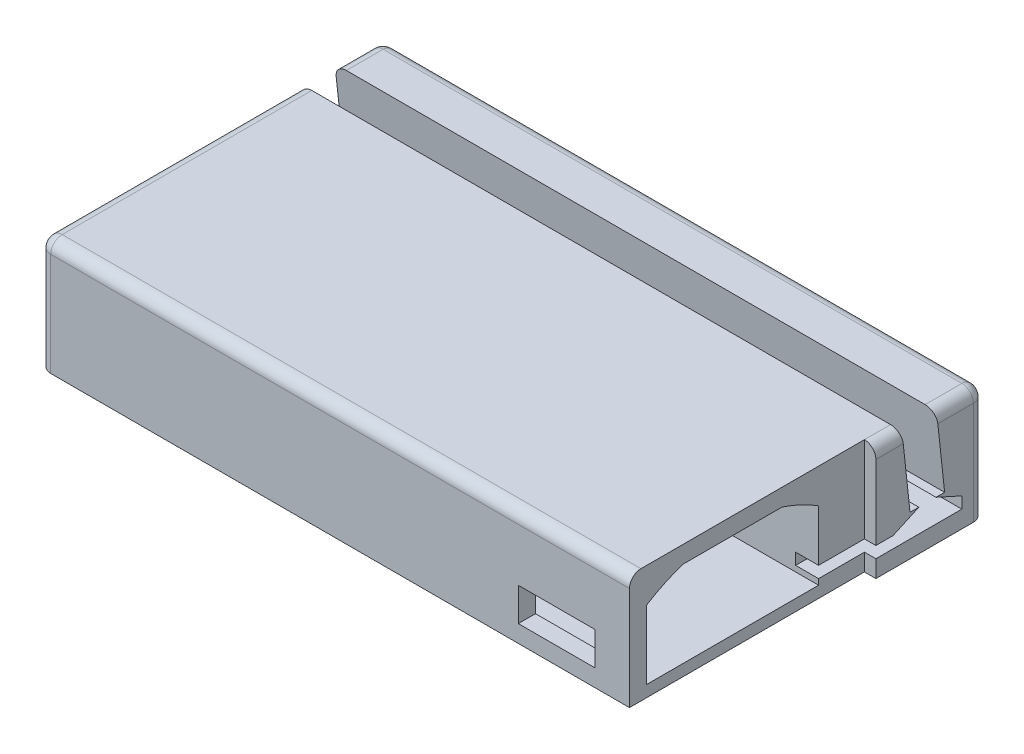
SolidWorks part; units mm, degrees
ref_plane "Přední rovina" through (0, 0, 0) normal (0, 0, 1) x (1, 0, 0)
ref_plane "Horní rovina" through (0, 0, 0) normal (0, 1, 0) x (1, 0, 0)
ref_plane "Pravá rovina" through (0, 0, 0) normal (1, 0, 0) x (0, 0, -1)
sketch "Skica2" plane through (0, 0, 0) normal (1, 0, 0) x (0, 0, -1)
  line L0 (15.5247, 10.31) -> (23, -2.961) construction
  line L1 (-30, 10) -> (30, 10)
  line L2 (-30, 10) -> (-30, -10)
  line L3 (-30, -10) -> (30, -10)
  line L4 (30, 10) -> (30, -10)
  line L5 (-30, 10) -> (30, -10) construction
  line L6 (-30, -10) -> (30, 10) construction
  line L7 (15.5247, 10.31) -> (21.4897, 10.9572)
  line L8 (15.5247, 10.31) -> (17.035, -3.6083)
  line L9 (17.035, -3.6083) -> (23, -2.961)
  line L10 (21.4897, 10.9572) -> (23, -2.961)
  line L16 (14, -7) -> (26, -7)
  line L17 (26, -7) -> (26, -4)
  line L33 (14, -4) -> (14, -7)
  line L34 (14, -7) -> (26, -4) construction
  line L35 (14, -4) -> (26, -7) construction
  line L36 (14, -4) -> (26, -4)
  line L46 (18.5, -2.961) -> (14, -5)
  line L47 (14, -5) -> (14, -2.961)
  line L48 (14, -2.961) -> (18.5, -2.961)
  line L49 (20, -4) -> (20, -7)
  line L50 (26, -5) -> (26, -2.961)
  line L51 (21.5, -2.961) -> (26, -5)
  line L52 (26, -2.961) -> (21.5, -2.961)
  line L54 (-16.965, -2.961) -> (-11, -2.961)
  line L56 (17.035, -3.6083) -> (23, -2.961)
  point P0 (0, 0)
  point P20 (19.2624, 3.6745)
  point P27 (20, -5.5)
  dimension "D1" = 60
  dimension "D2" = 20
  dimension "D3" = 14
  dimension "D4" = 6
  dimension "D5" = 12
  dimension "D6" = 3
  dimension "D7" = 4.5
  dimension "D8" = 3
  dimension "D9" = 2
  dimension "D10" = 3
  dimension "D11" = 10
  dimension "D12" = 3
  dimension "D14" = 4.039
extrude "Přidat vysunutím2" add sketch "Skica2" along normal blind 105 contours L52 L50 L17 L16 L33 L47 L48 L8 L1 L2 L3 L4 L10 | L46 L47 L48 | L51 L50 L52 region at (0, -0.0316, 2.3082)
sketch "Skica3" plane through (105, 0, 0) normal (1, 0, 0) x (0, 0, -1)
  line L0 (-30, 10) -> (-30, -10) construction
  line L1 (-27, 4) -> (3, 4)
  line L2 (-27, 4) -> (-27, -8)
  line L3 (-27, -8) -> (3, -8)
  line L4 (3, 4) -> (3, -8)
  line L7 (-30, 10) -> (15.5584, 10) construction
  dimension "D1" = 3
  dimension "D2" = 6
  dimension "D3" = 12
  dimension "D4" = 30
extrude "Odebrat vysunutím1" cut sketch "Skica3" against normal blind 102
sketch "Skica5" plane through (0, 0, -14) normal (0, 0, -1) x (-1, 0, 0)
  line L0 (-105, -7) -> (0, -7) construction
  line L1 (-99, -5) -> (-105, -5)
  line L2 (-99, -5) -> (-99, -7)
  line L3 (-99, -7) -> (-105, -7)
  line L4 (-105, -5) -> (-105, -7)
  line L6 (-105, 10) -> (-105, -10) construction
  dimension "D1" = 2
  dimension "D2" = 0
  dimension "D3" = 6
extrude "Odebrat vysunutím3" cut sketch "Skica5" against normal blind 15
sketch "Skica10" plane through (105, 0, 0) normal (1, 0, 0) x (0, 0, -1)
  line L0 (-30, 10) -> (-30, -10) construction
  line L1 (-30, 10) -> (15.5584, 10) construction
  line L2 (-27, 4) -> (3, 4)
  line L4 (-22, 9) -> (-2, 9)
  line L5 (-22, 9) -> (-22, 7)
  line L6 (-22, 7) -> (-2, 7)
  line L7 (-2, 9) -> (-2, 7)
  line L8 (-22, 9) -> (-2, 7) construction
  line L9 (-22, 7) -> (-2, 9) construction
  arc A1 (-27, 4) -> (3, 4) centre (-12, -19.6432) cw
  point P7 (-12, 8)
  point P12 (0, 0)
  point P13 (0, 0)
  line M21 (-27, 4) -> (3, 4)
  dimension "D1" = 30
  dimension "D2" = 3
  dimension "D4" = 28
  dimension "D5" = 3
  dimension "D3" = 6
  dimension "D6" = 2
  dimension "D7" = 20
extrude "Odebrat vysunutím6" cut sketch "Skica10" against normal blind 102 contours A1 L6 M21 region at (105, 5.3709, 12)
sketch "Skica12" plane through (105, 0, 0) normal (1, 0, 0) x (0, 0, -1)
  line L0 (-30, -10) -> (30, -10) construction
  line L1 (-30, 10) -> (11, 10)
  line L2 (-30, 10) -> (-30, -10)
  line L3 (-30, -10) -> (11, -10)
  line L4 (11, 10) -> (11, -10)
  line L6 (3, -8) -> (3, -7) construction
  dimension "D1" = 8
extrude "Odebrat vysunutím8" cut sketch "Skica12" against normal blind 2
sketch "Skica13" plane through (0, 0, 30) normal (0, 0, 1) x (1, 0, 0)
  line L0 (83.6, -7) -> (97, -1.2) construction
  line L1 (83.6, -7) -> (83.6, -1.2)
  line L2 (83.6, -7) -> (97, -7)
  line L3 (97, -7) -> (97, -1.2)
  line L4 (83.6, -1.2) -> (97, -1.2)
  line L5 (103, 10) -> (103, -10) construction
  line L6 (103, -10) -> (0, -10) construction
  dimension "D1" = 6
  dimension "D2" = 3
  dimension "D3" = 5.8
  dimension "D4" = 13.4
extrude "Odebrat vysunutím9" cut sketch "Skica13" against normal blind 10
fillet "Zaoblit1" radius 2 8 edges at (0, 0, 30) (0, 10, 7.2208) (105, 10, -13.2792) (105, 10, -25.7968) (0, 10, -25.7968) (0, 0, -30) (52.5, 10, -30) (105, 0, -30)
fillet "Zaoblit2" radius 2 2 edges at (0.5858, 9.4142, 29.4142) (52.5, 10, 30)
chamfer "Zkosení2" distance 3 angle 45 1 edges at (97, -4.1, 27)
